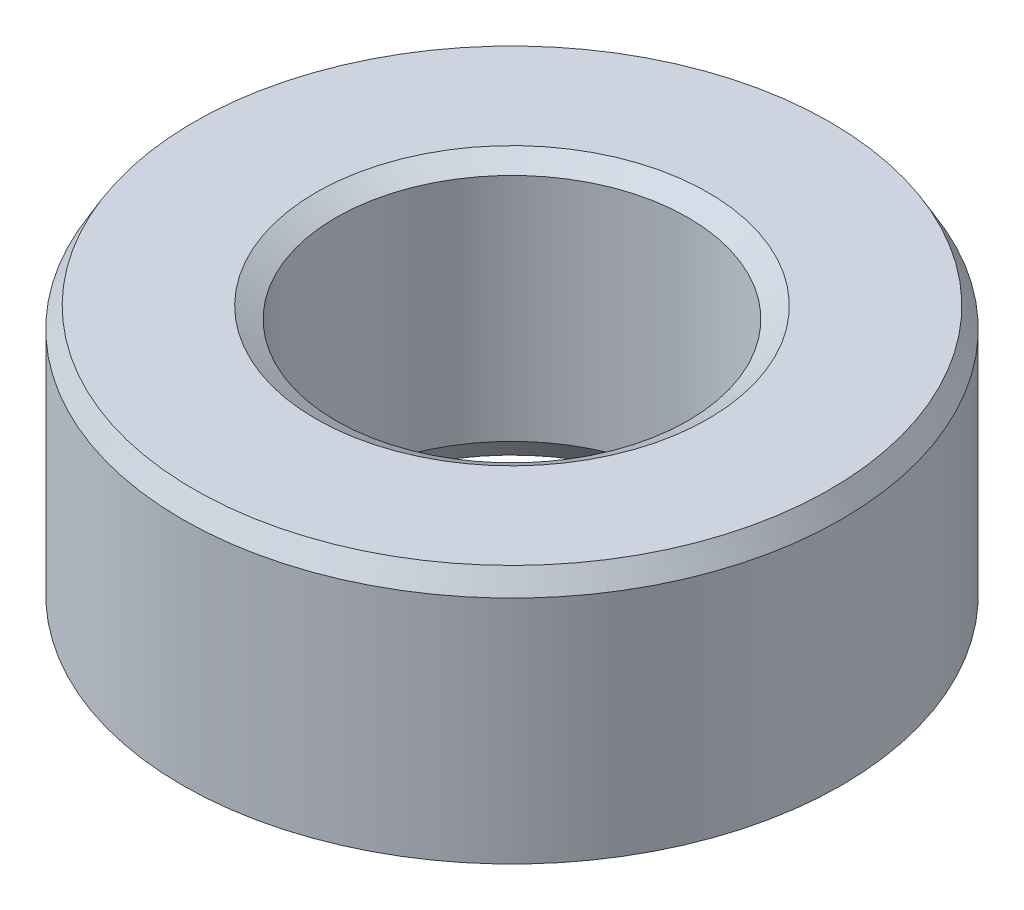
SolidWorks part; units mm, degrees
ref_plane "Front Plane" through (0, 0, 0) normal (0, 0, 1) x (1, 0, 0)
ref_plane "Top Plane" through (0, 0, 0) normal (0, 1, 0) x (1, 0, 0)
ref_plane "Right Plane" through (0, 0, 0) normal (1, 0, 0) x (0, 0, -1)
sketch "Sketch1" plane through (0, 0, 0) normal (0, 1, 0) x (1, 0, 0)
  circle A0 centre (0, 0) radius 42.5
  dimension "SLEEVE_OD" = 85
extrude "Boss-Extrude1" add sketch "Sketch1" along normal blind 33.7743
sketch "Sketch2" plane through (0, 0, 0) normal (0, 1, 0) x (1, 0, 0)
  circle A0 centre (0, 0) radius 22.6898
  dimension "BORE_D" = 45.3796
extrude "Cut-Extrude1" cut sketch "Sketch2" along normal through all
chamfer "Chamfer1" distance 2.5913 angle 30 4 edges at (0, 33.7743, 22.6898) (0, 0, 22.6898) (0, 0, 42.5) (0, 33.7743, 42.5) first distance on face at (0, 33.7743, 22.6898) first distance on face at (0, 0, 22.6898) first distance on face at (0, 33.7743, 42.5)
